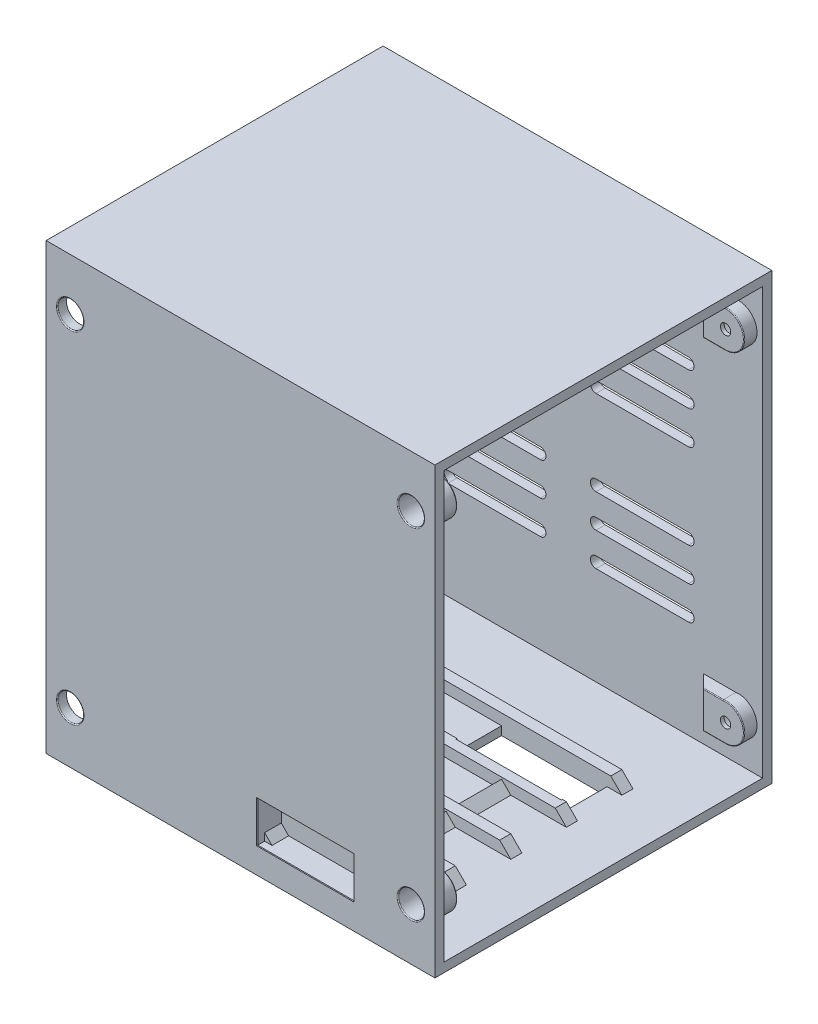
SolidWorks part; units mm, degrees
ref_plane "Front Plane" through (0, 0, 0) normal (0, 0, 1) x (1, 0, 0)
ref_plane "Top Plane" through (0, 0, 0) normal (0, 1, 0) x (1, 0, 0)
ref_plane "Right Plane" through (0, 0, 0) normal (1, 0, 0) x (0, 0, -1)
sketch "Sketch1" plane through (205.5525, 0, 0) normal (1, 0, 0) x (0, 0, -1)
  line L0 (1.5129, 48.8646) -> (1.513, -71.1354) construction
  line L1 (-89.4871, 48.8644) -> (1.5129, 48.8646) construction
  line L2 (-89.4871, 48.8644) -> (-89.487, -71.1356) construction
  line L3 (-89.487, -71.1356) -> (1.513, -71.1354) construction
  line L4 (1.5129, 48.8646) -> (1.513, -71.1354)
  line L5 (-89.4871, 48.8644) -> (1.5129, 48.8646)
  line L6 (-89.4871, 48.8644) -> (-89.487, -71.1356)
  line L7 (-89.487, -71.1356) -> (1.513, -71.1354)
  line L8 (-86.987, -68.6356) -> (-0.987, -68.6355)
  line L9 (-0.9871, 46.3645) -> (-0.987, -68.6355)
  line L10 (-86.9871, 46.3644) -> (-0.9871, 46.3645)
  line L11 (-86.9871, 46.3644) -> (-86.987, -68.6356)
  dimension "D1" = 2.5
extrude "Boss-Extrude1" add sketch "Sketch1" along normal up to surface (105 mm away)
sketch "Sketch2" plane through (0, 0, 86.9871) normal (0, 0, -1) x (-1, 0, 0)
  line L0 (-205.5525, 46.3645) -> (-205.5525, -68.6355) construction
  line L1 (-208.4525, -46.1353) -> (-206.5525, -46.1353)
  line L2 (-208.4525, -46.1353) -> (-208.4525, -40.1355)
  line L3 (-208.4525, -40.1355) -> (-206.5525, -40.1355)
  line L4 (-206.5525, -46.1353) -> (-206.5525, -40.1355)
  line L5 (-206.5525, 23.8645) -> (-208.4525, 23.8645)
  line L6 (-206.5525, 23.8645) -> (-206.5525, 17.8647)
  line L7 (-206.5525, 17.8647) -> (-208.4525, 17.8647)
  line L8 (-208.4525, 23.8645) -> (-208.4525, 17.8647)
  dimension "D1" = 0.1
  dimension "D2" = 1
  dimension "D3" = 0.1
  dimension "D4" = 1
  dimension "D5" = 0
  dimension "D6" = 0
  dimension "D7" = 0
  dimension "D8" = 0
extrude "Boss-Extrude2" add sketch "Sketch2" along normal offset from surface (1.3 mm away) 0.2
sketch "Sketch3" plane through (0, 0, 0.9871) normal (0, 0, 1) x (1, 0, 0)
  line L1 (210.0525, 28.8645) -> (225.0525, 28.8645)
  line L2 (210.0525, 28.8645) -> (210.0525, -51.1355)
  line L3 (210.0525, -51.1355) -> (225.0525, -51.1355)
  line L4 (225.0525, 28.8645) -> (225.0525, -51.1355)
  line L6 (205.5525, -68.6355) -> (205.5525, 46.3645) construction
  line L7 (310.5525, -71.1355) -> (205.5525, -71.1355) construction
  line L8 (310.5525, 48.8645) -> (205.5525, 48.8645) construction
  dimension "D1" = 4.5
  dimension "D2" = 15
  dimension "D3" = 20
  dimension "D4" = 20
extrude "Cut-Extrude1" cut sketch "Sketch3" against normal blind 0.5
sketch "Sketch4" plane through (0, 0, 0.9871) normal (0, 0, 1) x (1, 0, 0)
  line L0 (212.0525, 39.8645) -> (205.5525, 39.8645)
  line L1 (205.5525, -68.6355) -> (205.5525, 46.3645) construction
  line L2 (212.0525, 29.8645) -> (205.5525, 29.8645)
  line L3 (205.5525, 29.8645) -> (205.5525, 39.8645)
  line L4 (212.0525, -52.1355) -> (205.5525, -52.1355)
  line L5 (212.0525, -62.1355) -> (205.5525, -62.1355)
  line L6 (205.5525, -62.1355) -> (205.5525, -52.1355)
  line L7 (304.0525, -62.1355) -> (294.0525, -62.1355)
  line L8 (294.0525, -62.1355) -> (294.0525, -52.1855)
  line L9 (304.1025, -52.1855) -> (294.0525, -52.1855)
  line L10 (304.0525, 29.8645) -> (294.0525, 29.8645)
  line L11 (304.0525, 39.8645) -> (294.0525, 39.8645)
  line L12 (294.0525, 39.8645) -> (294.0525, 29.8645)
  circle A0 centre (212.0525, 34.8645) radius 2.25 construction
  circle A1 centre (212.0525, -57.1355) radius 2.25 construction
  circle A2 centre (212.0525, 34.8645) radius 2.25 construction
  circle A3 centre (212.0525, -57.1355) radius 2.25 construction
  circle A4 centre (212.0525, -57.1355) radius 5
  circle A5 centre (212.0525, 34.8645) radius 5
  circle A6 centre (212.0525, -57.1355) radius 3.5
  circle A7 centre (212.0525, 34.8645) radius 3.5
  circle A8 centre (212.0525, 34.8645) radius 1.4
  circle A9 centre (212.0525, -57.1355) radius 1.4
  circle A10 centre (304.0525, 34.8645) radius 1.6 construction
  circle A11 centre (304.0525, -57.1355) radius 1.6 construction
  circle A12 centre (304.0525, 34.8645) radius 1.6 construction
  circle A13 centre (304.0525, -57.1355) radius 1.6 construction
  circle A14 centre (304.0525, 34.8645) radius 5
  circle A15 centre (304.0525, -57.1355) radius 5
  circle A16 centre (304.0525, -57.1355) radius 3.5
  circle A17 centre (304.0525, -57.1355) radius 1.4
  circle A18 centre (304.0525, 34.8645) radius 3.5
  circle A19 centre (304.0525, 34.8645) radius 1.4
  line M7 (205.5525, 46.3645) -> (205.5525, -68.6355)
  dimension "D1" = 10
  dimension "D2" = 10
  dimension "D3" = 7
  dimension "D4" = 7
  dimension "D5" = 2.8
  dimension "D6" = 2.8
  dimension "D7" = 10
  dimension "D8" = 7
  dimension "D9" = 2.8
  dimension "D10" = 10
  dimension "D11" = 7
  dimension "D12" = 2.8
  dimension "D13" = 10
  dimension "D14" = 10
extrude "Boss-Extrude3" add sketch "Sketch4" along normal up to surface (3.5 mm away) contours A5 A7 | A4 A6 | A5 L0 L2 M7 | A4 L4 L5 M7 | A15 A16 | A14 A18 | A14 L11 L12 L10 | A15 L9 L8 L7 region at (206.9332, 34.8645, 0.9871) region at (208.8025, -52.2547, 0.9871) region at (215.488, 38.3001, 0.9871) region at (215.488, -53.6999, 0.9871) region at (299.2061, -57.479, 0.9871) region at (297.1787, -57.1748, 0.9871) region at (297.1915, 34.8645, 0.9871) region at (299.1939, 34.8645, 0.9871)
extrude "Boss-Extrude4" add sketch "Sketch4<3>" against normal blind 1 from surface contours A7 A8 | A18 A19 | A16 A17 | A6 A9 region at (208.6515, -57.1355, 0.9871) region at (208.6515, 34.8645, 0.9871) region at (300.6515, -57.1355, 0.9871) region at (300.6515, 34.8645, 0.9871) starting at face at (307.5525, 34.8645, 4.4871)
sketch "Sketch4<3>" plane through (0, 0, 0.9871) normal (0, 0, 1) x (1, 0, 0) same geometry as "Sketch4"
extrude "Cut-Extrude2" cut sketch "Sketch4<4>" against normal through all contours A6 A9 | A9 | A7 A8 | A8 | A17 | A16 A17 | A19 | A18 A19 region at (208.6515, -57.1355, 0.9871) region at (208.6515, 34.8645, 0.9871) region at (212.0525, 34.8645, 0.9871) region at (212.0525, -57.1355, 0.9871) region at (300.6515, -57.1355, 0.9871) region at (304.0525, -57.1355, 0.9871) region at (300.6515, 34.8645, 0.9871) region at (304.0525, 34.8645, 0.9871)
sketch "Sketch4<4>" plane through (0, 0, 0.9871) normal (0, 0, 1) x (1, 0, 0) same geometry as "Sketch4"
chamfer "Chamfer1" distance 4 angle 45 1 edges at (294.0525, -57.1605, 4.4871)
chamfer "Chamfer2" distance 4 angle 45 1 edges at (294.0525, 34.8645, 4.4871)
sketch "Sketch5" plane through (0, 0, -1.5129) normal (0, 0, -1) x (-1, 0, 0)
  line L0 (-258.0525, 48.8645) -> (-258.0525, -71.1355) construction
  line L1 (-310.5525, 48.8645) -> (-205.5525, 48.8645) construction
  line L2 (-310.5525, -71.1355) -> (-205.5525, -71.1355) construction
  line L3 (-310.5525, -11.1355) -> (-205.5525, -11.1355) construction
  line L4 (-310.5525, -71.1355) -> (-310.5525, 48.8645) construction
  line L5 (-205.5525, 48.8645) -> (-205.5525, -71.1355) construction
  line L6 (-290.5525, 10.8645) -> (-290.5525, 7.8645)
  line L7 (-290.5525, 1.8645) -> (-265.5525, 1.8645)
  line L8 (-290.5525, 1.8645) -> (-290.5525, -1.1355)
  line L9 (-290.5525, -1.1355) -> (-265.5525, -1.1355)
  line L10 (-265.5525, 1.8645) -> (-265.5525, -1.1355)
  line L11 (-290.5525, 10.8645) -> (-265.5525, 10.8645)
  line L12 (-265.5525, 10.8645) -> (-265.5525, 7.8645)
  line L13 (-290.5525, 7.8645) -> (-265.5525, 7.8645)
  line L14 (-290.5525, 19.8645) -> (-290.5525, 16.8645)
  line L15 (-290.5525, 19.8645) -> (-265.5525, 19.8645)
  line L16 (-265.5525, 19.8645) -> (-265.5525, 16.8645)
  line L17 (-290.5525, 16.8645) -> (-265.5525, 16.8645)
  line L18 (-225.5525, 16.8645) -> (-250.5525, 16.8645)
  line L19 (-250.5525, 19.8645) -> (-250.5525, 16.8645)
  line L20 (-225.5525, 19.8645) -> (-250.5525, 19.8645)
  line L21 (-225.5525, 19.8645) -> (-225.5525, 16.8645)
  line L22 (-225.5525, 7.8645) -> (-250.5525, 7.8645)
  line L23 (-250.5525, 10.8645) -> (-250.5525, 7.8645)
  line L24 (-225.5525, 10.8645) -> (-250.5525, 10.8645)
  line L25 (-250.5525, 1.8645) -> (-250.5525, -1.1355)
  line L26 (-225.5525, -1.1355) -> (-250.5525, -1.1355)
  line L27 (-225.5525, 1.8645) -> (-225.5525, -1.1355)
  line L28 (-225.5525, 1.8645) -> (-250.5525, 1.8645)
  line L29 (-225.5525, 10.8645) -> (-225.5525, 7.8645)
  line L30 (-225.5525, -33.1355) -> (-225.5525, -30.1355)
  line L31 (-225.5525, -24.1355) -> (-250.5525, -24.1355)
  line L32 (-225.5525, -24.1355) -> (-225.5525, -21.1355)
  line L33 (-225.5525, -21.1355) -> (-250.5525, -21.1355)
  line L34 (-250.5525, -24.1355) -> (-250.5525, -21.1355)
  line L35 (-225.5525, -33.1355) -> (-250.5525, -33.1355)
  line L36 (-250.5525, -33.1355) -> (-250.5525, -30.1355)
  line L37 (-225.5525, -30.1355) -> (-250.5525, -30.1355)
  line L38 (-225.5525, -42.1355) -> (-225.5525, -39.1355)
  line L39 (-225.5525, -42.1355) -> (-250.5525, -42.1355)
  line L40 (-250.5525, -42.1355) -> (-250.5525, -39.1355)
  line L41 (-225.5525, -39.1355) -> (-250.5525, -39.1355)
  line L42 (-290.5525, -39.1355) -> (-265.5525, -39.1355)
  line L43 (-265.5525, -42.1355) -> (-265.5525, -39.1355)
  line L44 (-290.5525, -42.1355) -> (-265.5525, -42.1355)
  line L45 (-290.5525, -42.1355) -> (-290.5525, -39.1355)
  line L46 (-290.5525, -30.1355) -> (-265.5525, -30.1355)
  line L47 (-265.5525, -33.1355) -> (-265.5525, -30.1355)
  line L48 (-290.5525, -33.1355) -> (-265.5525, -33.1355)
  line L49 (-265.5525, -24.1355) -> (-265.5525, -21.1355)
  line L50 (-290.5525, -21.1355) -> (-265.5525, -21.1355)
  line L51 (-290.5525, -24.1355) -> (-290.5525, -21.1355)
  line L52 (-290.5525, -24.1355) -> (-265.5525, -24.1355)
  line L53 (-290.5525, -33.1355) -> (-290.5525, -30.1355)
  arc A0 (-265.5525, 1.8645) -> (-265.5525, -1.1355) centre (-265.5525, 0.3645) cw
  arc A1 (-290.5525, -1.1355) -> (-290.5525, 1.8645) centre (-290.5525, 0.3645) cw
  arc A2 (-265.5525, 10.8645) -> (-265.5525, 7.8645) centre (-265.5525, 9.3645) cw
  arc A3 (-290.5525, 7.8645) -> (-290.5525, 10.8645) centre (-290.5525, 9.3645) cw
  arc A4 (-265.5525, 19.8645) -> (-265.5525, 16.8645) centre (-265.5525, 18.3645) cw
  arc A5 (-290.5525, 16.8645) -> (-290.5525, 19.8645) centre (-290.5525, 18.3645) cw
  arc A6 (-225.5525, 16.8645) -> (-225.5525, 19.8645) centre (-225.5525, 18.3645) ccw
  arc A7 (-250.5525, 19.8645) -> (-250.5525, 16.8645) centre (-250.5525, 18.3645) ccw
  arc A8 (-225.5525, 7.8645) -> (-225.5525, 10.8645) centre (-225.5525, 9.3645) ccw
  arc A9 (-250.5525, 10.8645) -> (-250.5525, 7.8645) centre (-250.5525, 9.3645) ccw
  arc A10 (-225.5525, -1.1355) -> (-225.5525, 1.8645) centre (-225.5525, 0.3645) ccw
  arc A11 (-250.5525, 1.8645) -> (-250.5525, -1.1355) centre (-250.5525, 0.3645) ccw
  arc A12 (-250.5525, -24.1355) -> (-250.5525, -21.1355) centre (-250.5525, -22.6355) cw
  arc A13 (-225.5525, -21.1355) -> (-225.5525, -24.1355) centre (-225.5525, -22.6355) cw
  arc A14 (-250.5525, -33.1355) -> (-250.5525, -30.1355) centre (-250.5525, -31.6355) cw
  arc A15 (-225.5525, -30.1355) -> (-225.5525, -33.1355) centre (-225.5525, -31.6355) cw
  arc A16 (-250.5525, -42.1355) -> (-250.5525, -39.1355) centre (-250.5525, -40.6355) cw
  arc A17 (-225.5525, -39.1355) -> (-225.5525, -42.1355) centre (-225.5525, -40.6355) cw
  arc A18 (-290.5525, -39.1355) -> (-290.5525, -42.1355) centre (-290.5525, -40.6355) ccw
  arc A19 (-265.5525, -42.1355) -> (-265.5525, -39.1355) centre (-265.5525, -40.6355) ccw
  arc A20 (-290.5525, -30.1355) -> (-290.5525, -33.1355) centre (-290.5525, -31.6355) ccw
  arc A21 (-265.5525, -33.1355) -> (-265.5525, -30.1355) centre (-265.5525, -31.6355) ccw
  arc A22 (-290.5525, -21.1355) -> (-290.5525, -24.1355) centre (-290.5525, -22.6355) ccw
  arc A23 (-265.5525, -24.1355) -> (-265.5525, -21.1355) centre (-265.5525, -22.6355) ccw
  dimension "D1" = 3
  dimension "D2" = 25
  dimension "D3" = 10
  dimension "D4" = 7.5
  dimension "D6" = 6
  dimension "D5" = 3
extrude "Cut-Extrude3" cut sketch "Sketch5" against normal blind 3 contours L14 L17 L16 L15 | A5 L14 | A4 L16 | A1 L8 | L10 L7 L8 L9 | A0 L10 | A2 L12 | L6 L13 L12 L11 | A3 L6 | A17 L38 | L38 L41 L40 L39 | A16 L40 | A14 L36 | L30 L37 L36 L35 | A15 L30 | A13 L32 | L34 L31 L32 L33 | A12 L34 | L51 A22 | L51 L52 L49 L50 | L49 A23 | L47 A21 | L53 L48 L47 L46 | L53 A20 | L45 A18 | L45 L44 L43 L42 | L43 A19 | L21 A6 | L21 L20 L19 L18 | L19 A7 | L23 A9 | L29 L24 L23 L22 | L29 A8 | L27 A10 | L27 L28 L25 L26 | L25 A11 region at (278.0525, 9.3645, -1.5129) region at (291.1891, 9.3645, -1.5129) region at (264.9159, 9.3645, -1.5129) region at (278.0525, 0.3645, -1.5129) region at (291.1891, 0.3645, -1.5129) region at (264.9159, 0.3645, -1.5129) region at (278.0525, 18.3645, -1.5129) region at (291.1891, 18.3645, -1.5129) region at (264.9159, 18.3645, -1.5129) region at (238.0525, 18.3645, -1.5129) region at (224.9159, 18.3645, -1.5129) region at (251.1891, 18.3645, -1.5129) region at (238.0525, 9.3645, -1.5129) region at (224.9159, 9.3645, -1.5129) region at (251.1891, 9.3645, -1.5129) region at (238.0525, 0.3645, -1.5129) region at (251.1891, 0.3645, -1.5129) region at (224.9159, 0.3645, -1.5129) region at (238.0525, -31.6355, -1.5129) region at (224.9159, -31.6355, -1.5129) region at (251.1891, -31.6355, -1.5129) region at (238.0525, -22.6355, -1.5129) region at (224.9159, -22.6355, -1.5129) region at (251.1891, -22.6355, -1.5129) region at (238.0525, -40.6355, -1.5129) region at (224.9159, -40.6355, -1.5129) region at (251.1891, -40.6355, -1.5129) region at (278.0525, -40.6355, -1.5129) region at (291.1891, -40.6355, -1.5129) region at (264.9159, -40.6355, -1.5129) region at (278.0525, -31.6355, -1.5129) region at (291.1891, -31.6355, -1.5129) region at (264.9159, -31.6355, -1.5129) region at (278.0525, -22.6355, -1.5129) region at (264.9159, -22.6355, -1.5129) region at (291.1891, -22.6355, -1.5129)
extrude "Boss-Extrude5" add sketch "Sketch4<6>" against normal up to surface (5 mm away) from surface contours A15 L9 L8 L7 | A15 A16 | A14 L11 L12 L10 | A14 A18 region at (299.2061, -57.479, 0.9871) region at (297.1787, -57.1748, 0.9871) region at (297.1915, 34.8645, 0.9871) region at (299.1939, 34.8645, 0.9871) starting at face at (258.0525, -11.1355, 86.9871)
sketch "Sketch4<6>" plane through (0, 0, 0.9871) normal (0, 0, 1) x (1, 0, 0) same geometry as "Sketch4"
extrude "Boss-Extrude6" add sketch "Sketch4<7>" along normal blind 1 from surface contours A14 A18 | A18 A19 | A16 A17 | A15 A16 region at (299.2061, -57.479, 0.9871) region at (299.1939, 34.8645, 0.9871) region at (300.6515, -57.1355, 0.9871) region at (300.6515, 34.8645, 0.9871) starting at face at (300.3025, 34.8645, 81.9871)
sketch "Sketch4<7>" plane through (0, 0, 0.9871) normal (0, 0, 1) x (1, 0, 0) same geometry as "Sketch4"
extrude "Cut-Extrude4" cut sketch "Sketch4<8>" along normal through all from surface contours A16 A17 | A18 A19 | A17 | A19 | A6 A9 | A9 | A7 A8 | A8 region at (208.6515, -57.1355, 0.9871) region at (208.6515, 34.8645, 0.9871) region at (212.0525, 34.8645, 0.9871) region at (212.0525, -57.1355, 0.9871) region at (300.6515, -57.1355, 0.9871) region at (304.0525, -57.1355, 0.9871) region at (300.6515, 34.8645, 0.9871) region at (304.0525, 34.8645, 0.9871) starting at face at (300.2112, -57.0658, 86.9871)
sketch "Sketch4<8>" plane through (0, 0, 0.9871) normal (0, 0, 1) x (1, 0, 0) same geometry as "Sketch4"
chamfer "Chamfer3" distance 5 angle 45 1 edges at (294.0525, -57.1605, 81.9871)
chamfer "Chamfer4" distance 5 angle 45 1 edges at (294.0525, 34.8645, 81.9871)
fillet "Fillet1" radius 0.25 9 edges at (307.5525, -57.1355, -1.5129) (307.5525, -57.1355, 3.4871) (307.5525, 34.8645, -1.5129) (215.5525, 34.8645, -1.5129) (215.5525, -57.1355, -1.5129) (304.0525, 38.3645, 89.4871) (212.0525, 38.3645, 89.4871) (212.0525, -53.6355, 89.4871) (304.0525, -53.6355, 89.4871)
sketch "Sketch6" plane through (0, -68.6355, 0) normal (0, 1, 0) x (1, 0, 0)
  line L0 (295.5525, -20.9871) -> (310.5525, -0.9871) construction
  line L1 (295.5525, -23.9871) -> (220.5525, -23.9871)
  line L2 (295.5525, -23.9871) -> (295.5525, -20.9871)
  line L3 (295.5525, -20.9871) -> (220.5525, -20.9871)
  line L4 (220.5525, -23.9871) -> (220.5525, -20.9871)
  line L5 (310.5525, -86.9871) -> (295.5525, -23.9871) construction
  line L6 (220.5525, -23.9871) -> (205.5525, -86.9871) construction
  line L7 (220.5525, -20.9871) -> (205.5525, -0.9871)
  line L8 (295.5525, -35.9871) -> (220.5525, -35.9871)
  line L9 (295.5525, -38.9871) -> (295.5525, -35.9871)
  line L10 (295.5525, -38.9871) -> (220.5525, -38.9871)
  line L11 (220.5525, -38.9871) -> (220.5525, -35.9871)
  line L12 (295.5525, -50.9871) -> (220.5525, -50.9871)
  line L13 (295.5525, -53.9871) -> (295.5525, -50.9871)
  line L14 (295.5525, -53.9871) -> (220.5525, -53.9871)
  line L15 (220.5525, -53.9871) -> (220.5525, -50.9871)
  line L41 (295.5525, -65.9871) -> (220.5525, -65.9871)
  line L42 (295.5525, -68.9871) -> (295.5525, -65.9871)
  line L43 (295.5525, -68.9871) -> (220.5525, -68.9871)
  line L44 (220.5525, -68.9871) -> (220.5525, -65.9871)
  dimension "D1" = 3
  dimension "D2" = 75
  dimension "D5" = 20
  dimension "D6" = 12
  dimension "D3" = 4
  dimension "D4" = 1
extrude "Boss-Extrude7" add sketch "Sketch6" along normal blind 3 contours L15 L14 L13 L12 | L11 L10 L9 L8 | L3 L2 L1 L4 | L41 L44 L43 L42 region at (258.0525, -68.6355, 37.4871) region at (258.0525, -68.6355, 52.4871)
chamfer "Chamfer5" distance 3 angle 45 8 edges at (295.5525, -65.6355, 37.4871) (295.5525, -65.6355, 22.4871) (220.5525, -65.6355, 22.4871) (220.5525, -65.6355, 37.4871) (220.5525, -65.6355, 52.4871) (295.5525, -65.6355, 52.4871) (220.5525, -65.6355, 67.4871) (295.5525, -65.6355, 67.4871)
sketch "Sketch7" plane through (0, -68.6355, 0) normal (0, 1, 0) x (1, 0, 0)
  line L1 (280.5525, -68.9871) -> (275.5525, -68.9871)
  line L2 (280.5525, -68.9871) -> (280.5525, -20.9871)
  line L3 (280.5525, -20.9871) -> (275.5525, -20.9871)
  line L4 (275.5525, -68.9871) -> (275.5525, -20.9871)
  line L6 (295.5525, -68.9871) -> (220.5525, -68.9871) construction
  line L7 (245.5525, -68.9871) -> (240.5525, -68.9871)
  line L8 (245.5525, -68.9871) -> (245.5525, -20.9871)
  line L9 (245.5525, -20.9871) -> (240.5525, -20.9871)
  line L10 (240.5525, -68.9871) -> (240.5525, -20.9871)
  line L11 (295.5525, -20.9871) -> (220.5525, -20.9871) construction
  point P4 (243.3897, -63.0332)
  point P5 (243.483, -68.9871)
  point P6 (240.5525, -21.1355)
  point P7 (240.5525, -20.9871)
  point P12 (280.5525, -53.9871)
  point P15 (285.0256, -64.6728)
  point P16 (282.5301, -69.6233)
  point P17 (282.7269, -68.9871)
  point P21 (0, 0)
  point P23 (275.5525, -20.9871)
  point P24 (0, 0)
  point P25 (275.5525, -20.9871)
  point P28 (0, 0)
  line M2 (220.5525, -50.9871) -> (295.5525, -50.9871)
  line M4 (295.5525, -53.9871) -> (220.5525, -53.9871)
  line M8 (295.5525, -23.9871) -> (220.5525, -23.9871)
  line M18 (220.5525, -35.9871) -> (295.5525, -35.9871)
  line M20 (295.5525, -38.9871) -> (220.5525, -38.9871)
  line M37 (220.5525, -65.9871) -> (295.5525, -65.9871)
  dimension "D1" = 5
  dimension "D2" = 5
  dimension "D3" = 15
  dimension "D4" = 20
extrude "Boss-Extrude8" add sketch "Sketch7" along normal blind 2.5 contours L4 L2 M2 M20 | L4 L2 M18 M8 | L4 L2 M37 M4 | L10 L8 M37 M4 | L10 L8 M2 M20 | L10 L8 M18 M8 region at (278.0525, -68.6355, 59.9871) region at (243.0525, -68.6355, 59.9871) region at (278.0525, -68.6355, 44.9871) region at (243.0525, -68.6355, 44.9871) region at (278.0525, -68.6355, 29.9871) region at (243.0525, -68.6355, 29.9871)
chamfer "Chamfer6" distance 2.5 angle 45 12 edges at (240.5525, -66.1355, 59.9871) (245.5525, -66.1355, 59.9871) (240.5525, -66.1355, 44.9871) (245.5525, -66.1355, 44.9871) (240.5525, -66.1355, 29.9871) (245.5525, -66.1355, 29.9871) (275.5525, -66.1355, 29.9871) (280.5525, -66.1355, 29.9871) (275.5525, -66.1355, 44.9871) (280.5525, -66.1355, 44.9871) (275.5525, -66.1355, 59.9871) (280.5525, -66.1355, 59.9871)
extrude "Boss-Extrude9" add sketch "Sketch6<3>" against normal blind 3 from surface contours L4 L1 L2 L3 | L11 L10 L9 L8 | L15 L14 L13 L12 | L44 L43 L42 L41 region at (258.0525, -68.6355, 22.4871) region at (258.0525, -68.6355, 37.4871) region at (258.0525, -68.6355, 52.4871) region at (258.0525, -68.6355, 67.4871) starting at face at (258.0525, 46.3645, 43.9871)
sketch "Sketch6<3>" plane through (0, -68.6355, 0) normal (0, 1, 0) x (1, 0, 0) same geometry as "Sketch6"
sketch "Sketch8" plane through (0, 43.3645, 0) normal (0, -1, 0) x (1, 0, 0)
  line L1 (220.5525, 50.9871) -> (235.5525, 50.9871)
  line L2 (220.5525, 50.9871) -> (220.5525, 68.9871)
  line L3 (220.5525, 68.9871) -> (235.5525, 68.9871)
  line L4 (235.5525, 50.9871) -> (235.5525, 68.9871)
  line L5 (295.5525, 68.9871) -> (220.5525, 68.9871) construction
  dimension "D1" = 15
extrude "Cut-Extrude5" cut sketch "Sketch8" against normal up to surface (3 mm away) up to face at (258.0525, 46.3645, 22.4871)
chamfer "Chamfer7" distance 3 angle 45 8 edges at (295.5525, 43.3645, 52.4871) (235.5525, 43.3645, 52.4871) (295.5525, 43.3645, 22.4871) (220.5525, 43.3645, 22.4871) (220.5525, 43.3645, 37.4871) (295.5525, 43.3645, 37.4871) (235.5525, 43.3645, 67.4871) (295.5525, 43.3645, 67.4871)
extrude "Boss-Extrude10" add sketch "Sketch7<2>" against normal blind 2.5 from surface starting at face at (265.5525, 46.3645, 67.4871)
sketch "Sketch7<2>" plane through (0, -68.6355, 0) normal (0, 1, 0) x (1, 0, 0) same geometry as "Sketch7"
chamfer "Chamfer8" distance 2.5 angle 45 12 edges at (280.5525, 43.8645, 44.9871) (275.5525, 43.8645, 44.9871) (240.5525, 43.8645, 44.9871) (245.5525, 43.8645, 44.9871) (280.5525, 43.8645, 59.9871) (275.5525, 43.8645, 59.9871) (245.5525, 43.8645, 59.9871) (240.5525, 43.8645, 59.9871) (240.5525, 43.8645, 29.9871) (245.5525, 43.8645, 29.9871) (275.5525, 43.8645, 29.9871) (280.5525, 43.8645, 29.9871)
sketch "Sketch9" plane through (0, 0, 86.9871) normal (0, 0, -1) x (-1, 0, 0)
  line L0 (-310.5525, -68.6355) -> (-295.5525, -12.6355) construction
  line L1 (-295.5525, -9.6355) -> (-220.5525, -9.6355)
  line L2 (-295.5525, -9.6355) -> (-295.5525, -12.6355)
  line L3 (-295.5525, -12.6355) -> (-220.5525, -12.6355)
  line L4 (-220.5525, -9.6355) -> (-220.5525, -12.6355)
  line L5 (-310.5525, 46.3645) -> (-295.5525, -9.6355) construction
  line L6 (-205.5525, 46.3645) -> (-220.5525, -9.6355) construction
  line L7 (-205.5525, -68.6355) -> (-220.5525, -12.6355) construction
  line L8 (-295.5525, 5.3645) -> (-220.5525, 5.3645)
  line L9 (-295.5525, 2.3645) -> (-220.5525, 2.3645)
  line L10 (-295.5525, 5.3645) -> (-295.5525, 2.3645)
  line L11 (-220.5525, 5.3645) -> (-220.5525, 2.3645)
  line L12 (-295.5525, 20.3645) -> (-220.5525, 20.3645)
  line L13 (-295.5525, 17.3645) -> (-220.5525, 17.3645)
  line L14 (-295.5525, 20.3645) -> (-295.5525, 17.3645)
  line L15 (-220.5525, 20.3645) -> (-220.5525, 17.3645)
  line L16 (-295.5525, -9.6355) -> (-220.5525, -9.6355)
  line L17 (-295.5525, -12.6355) -> (-220.5525, -12.6355)
  line L18 (-295.5525, -9.6355) -> (-295.5525, -12.6355)
  line L19 (-220.5525, -9.6355) -> (-220.5525, -12.6355)
  line L20 (-295.5525, 5.3645) -> (-220.5525, 5.3645)
  line L21 (-295.5525, 2.3645) -> (-220.5525, 2.3645)
  line L22 (-295.5525, 5.3645) -> (-295.5525, 2.3645)
  line L23 (-220.5525, 5.3645) -> (-220.5525, 2.3645)
  line L24 (-295.5525, -24.6355) -> (-220.5525, -24.6355)
  line L25 (-295.5525, -27.6355) -> (-220.5525, -27.6355)
  line L26 (-295.5525, -24.6355) -> (-295.5525, -27.6355)
  line L27 (-220.5525, -24.6355) -> (-220.5525, -27.6355)
  line L28 (-295.5525, -9.6355) -> (-220.5525, -9.6355)
  line L29 (-295.5525, -12.6355) -> (-220.5525, -12.6355)
  line L30 (-295.5525, -9.6355) -> (-295.5525, -12.6355)
  line L31 (-220.5525, -9.6355) -> (-220.5525, -12.6355)
  line L32 (-295.5525, -24.6355) -> (-220.5525, -24.6355)
  line L33 (-295.5525, -27.6355) -> (-220.5525, -27.6355)
  line L34 (-295.5525, -24.6355) -> (-295.5525, -27.6355)
  line L35 (-220.5525, -24.6355) -> (-220.5525, -27.6355)
  line L36 (-295.5525, -39.6355) -> (-220.5525, -39.6355)
  line L37 (-295.5525, -42.6355) -> (-220.5525, -42.6355)
  line L38 (-295.5525, -39.6355) -> (-295.5525, -42.6355)
  line L39 (-220.5525, -39.6355) -> (-220.5525, -42.6355)
  dimension "D1" = 3
  dimension "D2" = 75
  dimension "D3" = 3
  dimension "D4" = 3
extrude "Boss-Extrude11" add sketch "Sketch9" along normal blind 3 contours L15 L12 L14 L13 | L11 L8 L10 L9 | L4 L1 L2 L3 | L27 L24 L26 L25 | L36 L39 L37 L38 region at (258.0525, -11.1355, 86.9871) region at (258.0525, 3.8645, 86.9871) region at (258.0525, 18.8645, 86.9871) region at (258.0525, -26.1355, 86.9871)
chamfer "Chamfer9" distance 3 angle 45 10 edges at (295.5525, 3.8645, 83.9871) (295.5525, -11.1355, 83.9871) (295.5525, -26.1355, 83.9871) (295.5525, -41.1355, 83.9871) (220.5525, -41.1355, 83.9871) (220.5525, -26.1355, 83.9871) (220.5525, -11.1355, 83.9871) (220.5525, 3.8645, 83.9871) (220.5525, 18.8645, 83.9871) (295.5525, 18.8645, 83.9871)
sketch "Sketch10" plane through (0, 0, 86.9871) normal (0, 0, -1) x (-1, 0, 0)
  line L0 (-295.5525, -42.6355) -> (-220.5525, -42.6355) construction
  line L1 (-280.5525, -42.6355) -> (-275.5525, -42.6355)
  line L2 (-280.5525, -42.6355) -> (-280.5525, 20.3645)
  line L3 (-280.5525, 20.3645) -> (-275.5525, 20.3645)
  line L4 (-275.5525, -42.6355) -> (-275.5525, 20.3645)
  line L5 (-295.5525, 20.3645) -> (-220.5525, 20.3645) construction
  line L7 (-240.5525, 20.3645) -> (-235.5525, 20.3645)
  line L8 (-240.5525, 20.3645) -> (-240.5525, -42.6355)
  line L9 (-240.5525, -42.6355) -> (-235.5525, -42.6355)
  line L10 (-235.5525, 20.3645) -> (-235.5525, -42.6355)
  point P12 (-235.5525, -42.6355)
  dimension "D1" = 5
  dimension "D2" = 15
  dimension "D3" = 5
  dimension "D4" = 15
extrude "Boss-Extrude12" add sketch "Sketch10" along normal blind 2.5
chamfer "Chamfer10" distance 2.5 angle 45 16 edges at (240.5525, -33.6355, 84.4871) (235.5525, -33.6355, 84.4871) (235.5525, -18.6355, 84.4871) (240.5525, -18.6355, 84.4871) (240.5525, -3.6355, 84.4871) (235.5525, -3.6355, 84.4871) (235.5525, 11.3645, 84.4871) (240.5525, 11.3645, 84.4871) (275.5525, -3.6355, 84.4871) (275.5525, -18.6355, 84.4871) (275.5525, -33.6355, 84.4871) (280.5525, -33.6355, 84.4871) (280.5525, -18.6355, 84.4871) (280.5525, -3.6355, 84.4871) (275.5525, 11.3645, 84.4871) (280.5525, 11.3645, 84.4871)
sketch "Sketch11" plane through (0, -68.6355, 0) normal (0, 1, 0) x (1, 0, 0)
  line L1 (263.0525, -23.9871) -> (291.5525, -23.9871)
  line L2 (263.0525, -23.9871) -> (263.0525, -36.2871)
  line L3 (263.0525, -36.2871) -> (291.5525, -36.2871)
  line L4 (291.5525, -23.9871) -> (291.5525, -36.2871)
  line L6 (275.5525, -23.9871) -> (245.5525, -23.9871) construction
  point P4 (267.0525, -23.9871)
  point P6 (294.5474, -36.2871)
  point P7 (295.5525, -23.9871)
  point P8 (295.5525, -23.9871)
  point P9 (0, 0)
  point P11 (0, 0)
  point P13 (0, 0)
  point P14 (293.5637, -23.9871)
  line M33 (295.5525, -23.9871) -> (280.5525, -23.9871)
  line M35 (280.5525, -35.9871) -> (295.5525, -35.9871)
  line M36 (295.5525, -35.9871) -> (295.5525, -38.9871)
  line M47 (280.5525, -23.9871) -> (280.5525, -35.9871)
  dimension "D1" = 12.3
  dimension "D2" = 28.5
  dimension "D3" = 4
extrude "Cut-Extrude7" cut sketch "Sketch11" against normal blind 5 and the other way blind 4 contours L4 M33 M47 M35 | L2 L3 L1 M36 M35 M47 region at (272.0176, -68.6355, 30.2277) region at (286.0525, -68.6355, 29.9871)
chamfer "Chamfer11" distance 0.2 angle 45 4 edges at (263.0525, -71.1355, 30.1371) (277.3025, -71.1355, 23.9871) (291.5525, -71.1355, 30.1371) (277.3025, -71.1355, 36.2871)
sketch "Sketch13" plane through (0, 0, -1.5129) normal (0, 0, -1) x (-1, 0, 0)
  line L0 (-310.5525, 48.8645) -> (-288.0525, 36.3645) construction
  line L1 (-205.5525, 48.8645) -> (-228.0525, 36.3645) construction
  line L2 (-228.0525, -58.6355) -> (-205.5525, -71.1355) construction
  line L3 (-288.0525, -58.6355) -> (-310.5525, -71.1355) construction
  line L4 (-310.5525, 48.8645) -> (-205.5525, 48.8645) construction
  line L5 (-205.5525, -71.1355) -> (-205.5525, 48.8645) construction
  circle A0 centre (-228.0525, 36.3645) radius 5.15
  circle A1 centre (-228.0525, -58.6355) radius 5.15
  circle A2 centre (-288.0525, -58.6355) radius 5.15
  circle A3 centre (-288.0525, 36.3645) radius 5.15
  point P9 (-284.1241, -52.0869)
  point P13 (-287.2812, -58.5666)
  point P22 (-228.5044, 36.5383)
  dimension "D3" = 10.3
  dimension "D1" = 12.5
  dimension "D2" = 22.5
extrude "Cut-Extrude8" cut sketch "Sketch13" against normal offset from surface (1.75 mm away) 0.75 up to face at (278.0525, -31.6355, 0.9871)
sketch "Sketch14" plane through (0, 0, 86.9871) normal (0, 0, -1) x (-1, 0, 0)
  line L0 (-310.5525, -68.6355) -> (-205.5525, -68.6355) construction
  line L1 (-290.5525, -51.1355) -> (-260.5525, -51.1355)
  line L2 (-290.5525, -51.1355) -> (-290.5525, -66.1355)
  line L3 (-290.5525, -66.1355) -> (-260.5525, -66.1355)
  line L4 (-260.5525, -51.1355) -> (-260.5525, -66.1355)
  line L5 (-310.5525, -68.6355) -> (-310.5525, 46.3645) construction
  dimension "D1" = 30
  dimension "D2" = 15
  dimension "D3" = 2.5
  dimension "D4" = 20
extrude "Boss-Extrude13" add sketch "Sketch14" along normal blind 6
chamfer "Chamfer12" distance 6 angle 45 1 edges at (260.5525, -58.6355, 86.9871)
sketch "Sketch15" plane through (0, 0, 80.9871) normal (0, 0, -1) x (-1, 0, 0)
  line L8 (-288.5525, -53.1355) -> (-288.5525, -64.1355)
  line L9 (-288.5525, -64.1355) -> (-262.5525, -64.1355)
  line L10 (-262.5525, -64.1355) -> (-262.5525, -53.1355)
  line L11 (-262.5525, -53.1355) -> (-288.5525, -53.1355)
  line L12 (-288.5525, -53.1355) -> (-288.5525, -64.1355)
  line L13 (-288.5525, -64.1355) -> (-262.5525, -64.1355)
  line L14 (-262.5525, -64.1355) -> (-262.5525, -53.1355)
  line L15 (-262.5525, -53.1355) -> (-288.5525, -53.1355)
  dimension "D1" = 2
extrude "Cut-Extrude9" cut sketch "Sketch15" along normal offset from surface (6.5 mm away) 2 from surface up to face at (275.5525, -58.6355, 80.9871) starting at face at (304.0525, 38.6145, 89.4871)
chamfer "Chamfer13" distance 0.15 angle 45 4 edges at (288.5525, -58.6355, 89.4871) (275.5525, -64.1355, 89.4871) (262.5525, -58.6355, 89.4871) (275.5525, -53.1355, 89.4871)
sketch "Sketch16" plane through (0, 0, 82.9871) normal (0, 0, 1) x (1, 0, 0)
  line L0 (262.5525, -53.1355) -> (262.5525, -55.1355)
  line L1 (262.5525, -64.1355) -> (262.5525, -53.1355) construction
  line L2 (262.5525, -55.1355) -> (264.5525, -53.1355)
  line L3 (262.5525, -53.1355) -> (288.5525, -53.1355) construction
  line L4 (264.5525, -53.1355) -> (262.5525, -53.1355)
  line L5 (262.5525, -64.1355) -> (262.5525, -62.1355)
  line L6 (262.5525, -62.1355) -> (264.5525, -64.1355)
  line L7 (288.5525, -64.1355) -> (262.5525, -64.1355) construction
  line L8 (264.5525, -64.1355) -> (262.5525, -64.1355)
  line L9 (288.5525, -64.1355) -> (288.5525, -62.1355)
  line L10 (288.5525, -53.1355) -> (288.5525, -64.1355) construction
  line L11 (288.5525, -62.1355) -> (286.5525, -64.1355)
  line L12 (286.5525, -64.1355) -> (288.5525, -64.1355)
  line L13 (288.5525, -55.1355) -> (286.5525, -53.1355)
  line L14 (286.5525, -53.1355) -> (288.5525, -53.1355)
  line L15 (288.5525, -53.1355) -> (288.5525, -55.1355)
  dimension "D1" = 2
extrude "Boss-Extrude14" add sketch "Sketch16" along normal offset from surface (4.5 mm away) 2 up to face at (275.5525, -58.6355, 89.4871)
fillet "Fillet2" radius 0.2 18 edges at (301.0525, 29.8645, 4.4871) (309.0525, 34.8645, 4.4871) (301.0525, -62.1355, 4.4871) (208.8025, 39.8645, 4.4871) (217.0525, 34.8645, 4.4871) (208.8025, -62.1355, 4.4871) (217.0525, -57.1355, 4.4871) (301.0525, 39.8645, 4.4871) (300.6998, -52.1855, 4.4871) (309.04, -56.7819, 4.4871) (208.8025, 29.8645, 4.4871) (208.8025, -52.1355, 4.4871) (301.5525, -62.1355, 81.9871) (301.5525, 39.8645, 81.9871) (301.5525, 29.8645, 81.9871) (301.1998, -52.1855, 81.9871) (309.04, -56.7819, 81.9871) (309.0525, 34.8645, 81.9871)
equation "\"R\"=9.03994"
equation "\"R_MOUNT_OUTER\"=10"
equation "\"D1@Sketch4\"=\"R_MOUNT_OUTER\""
equation "\"D2@Sketch4\"=\"R_MOUNT_OUTER\""
equation "\"R_MOUNT_INNER\"=7"
equation "\"D3@Sketch4\"=\"R_MOUNT_INNER\""
equation "\"D4@Sketch4\"=\"R_MOUNT_INNER\""
equation "\"R_SCREW\" = 2.8"
equation "\"D5@Sketch4\"=\"R_SCREW\""
equation "\"D6@Sketch4\"=\"R_SCREW\""
equation "\"D7@Sketch4\"=\"R_MOUNT_OUTER\""
equation "\"D8@Sketch4\"=\"R_MOUNT_INNER\""
equation "\"D9@Sketch4\"=\"R_SCREW\""
equation "\"D10@Sketch4\"=\"R_MOUNT_OUTER\""
equation "\"D11@Sketch4\"=\"R_MOUNT_INNER\""
equation "\"D12@Sketch4\"=\"R_SCREW\""
